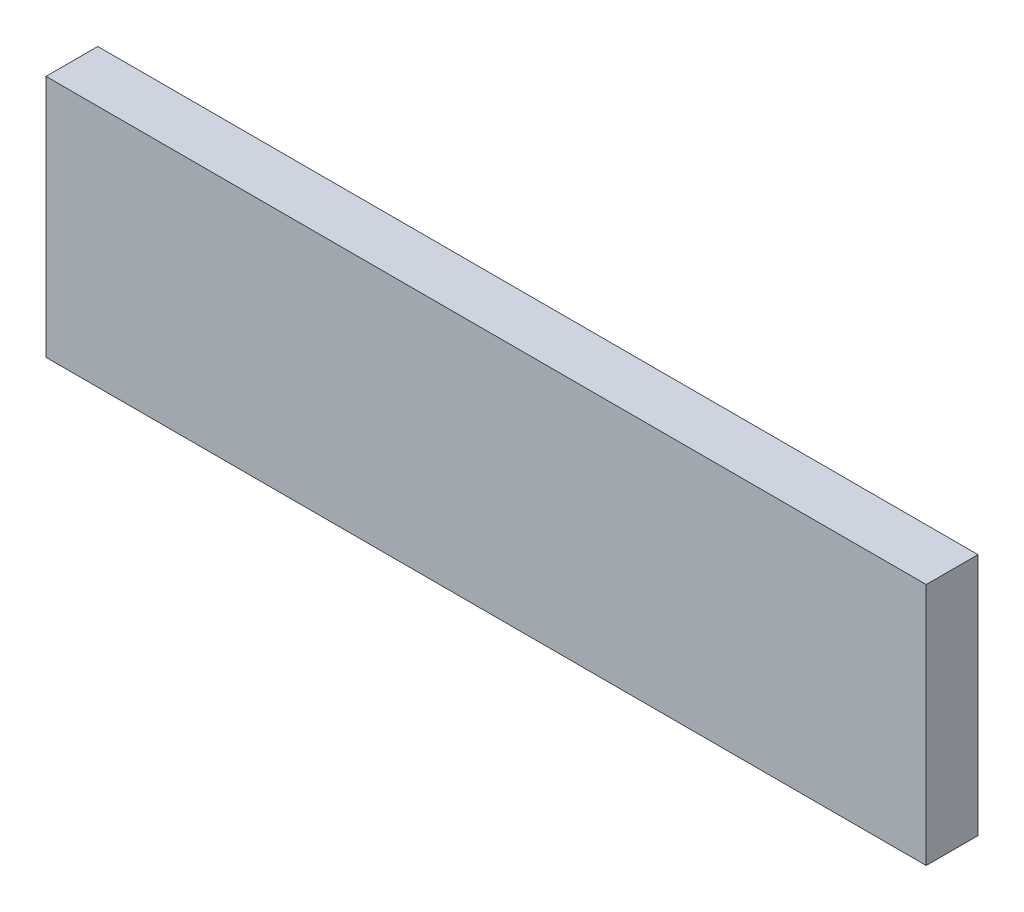
SolidWorks part; units mm, degrees
ref_plane "Front Plane" through (0, 0, 0) normal (0, 0, 1) x (1, 0, 0)
ref_plane "Top Plane" through (0, 0, 0) normal (0, 1, 0) x (1, 0, 0)
ref_plane "Right Plane" through (0, 0, 0) normal (1, 0, 0) x (0, 0, -1)
sketch "Sketch1" plane through (0, 0, 0) normal (0, 0, 1) x (1, 0, 0)
  line L1 (0, 0) -> (170, 0)
  line L2 (0, 0) -> (0, 47)
  line L3 (0, 47) -> (170, 47)
  line L4 (170, 0) -> (170, 47)
  dimension "D1" = 170
  dimension "D2" = 47
extrude "Boss-Extrude1" add sketch "Sketch1" along normal blind 10
